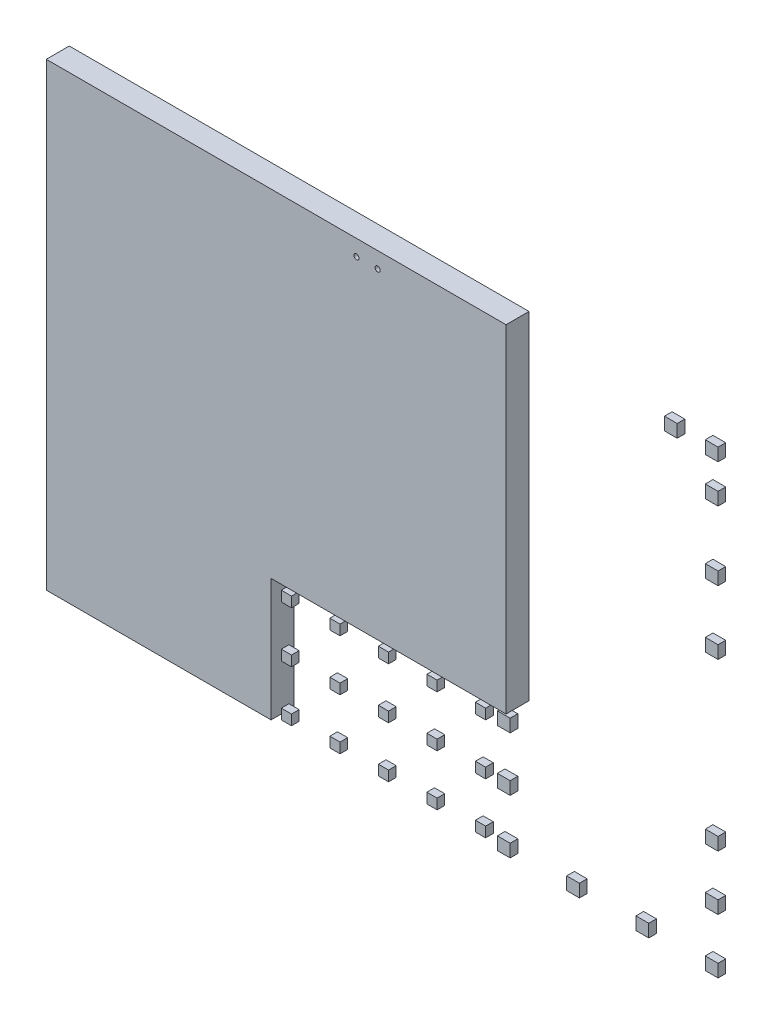
SolidWorks part; units mm, degrees
ref_plane "Спереди" through (0, 0, 0) normal (0, 0, 1) x (1, 0, 0)
ref_plane "Сверху" through (0, 0, 0) normal (0, 1, 0) x (1, 0, 0)
ref_plane "Справа" through (0, 0, 0) normal (1, 0, 0) x (0, 0, -1)
sketch "Эскиз1" plane through (0, 0, 0) normal (0, 0, 1) x (1, 0, 0)
  line L0 (0, 0) -> (9000, 0)
  line L1 (9000, 0) -> (9000, -6600)
  line L2 (9000, -6600) -> (4400, -6600)
  line L3 (4400, -6600) -> (4400, -9000)
  line L4 (4400, -9000) -> (0, -9000)
  line L5 (0, -9000) -> (0, 0)
  line L6 (8830, -6600) -> (8830, -9000) construction
  line L7 (8830, -9000) -> (9080, -9000)
  line L8 (8830, -9000) -> (8830, -8750)
  line L9 (8830, -8750) -> (9080, -8750)
  line L14 (9080, -9000) -> (9080, -8750)
  line L15 (9000, -203) -> (9000, -2700) construction
  line L16 (8797, -6600) -> (4400, -6600) construction
  line L17 (4400, -8797) -> (4400, -6603) construction
  line L18 (203, -9000) -> (4200, -9000) construction
  line L19 (8830, -6630) -> (9080, -6630)
  line L20 (8830, -6630) -> (8830, -6880)
  line L21 (8830, -6880) -> (9080, -6880)
  line L22 (9080, -6630) -> (9080, -6880)
  line L23 (9080, -6880) -> (9080, -7690) construction
  line L24 (8830, -7690) -> (9080, -7690)
  line L25 (8830, -7690) -> (8830, -7940)
  line L26 (8830, -7940) -> (9080, -7940)
  line L27 (9080, -7690) -> (9080, -7940)
  line L28 (9080, -7940) -> (9080, -8750) construction
  line L29 (13150, -9000) -> (0, -9000) construction
  line L30 (10186.6667, -8750) -> (10436.6667, -8750)
  line L31 (10186.6667, -8750) -> (10186.6667, -9000)
  line L32 (10186.6667, -9000) -> (10436.6667, -9000)
  line L33 (10436.6667, -8750) -> (10436.6667, -9000)
  line L34 (9080, -8750) -> (10186.6667, -8750) construction
  line L35 (11543.3333, -8750) -> (11793.3333, -8750)
  line L36 (11543.3333, -8750) -> (11543.3333, -9000)
  line L37 (11543.3333, -9000) -> (11793.3333, -9000)
  line L38 (11793.3333, -8750) -> (11793.3333, -9000)
  line L43 (12900, -8750) -> (13150, -8750)
  line L44 (12900, -8750) -> (12900, -9000)
  line L45 (12900, -9000) -> (13150, -9000)
  line L46 (13150, -8750) -> (13150, -9000)
  line L47 (10436.6667, -8750) -> (11543.3333, -8750) construction
  line L48 (11793.3333, -8750) -> (12900, -8750) construction
  line L49 (13150, -4500) -> (13150, -9000) construction
  line L50 (13150, -6600) -> (12900, -6600)
  line L51 (13150, -6600) -> (13150, -6850)
  line L52 (13150, -6850) -> (12900, -6850)
  line L53 (12900, -6600) -> (12900, -6850)
  line L54 (13150, -7675) -> (12900, -7675)
  line L55 (13150, -7675) -> (13150, -7925)
  line L56 (13150, -7925) -> (12900, -7925)
  line L57 (12900, -7675) -> (12900, -7925)
  line L58 (12900, -7675) -> (12900, -6850) construction
  line L59 (13150, -3600) -> (12900, -3600)
  line L60 (13150, -3600) -> (13150, -3350)
  line L61 (13150, -3350) -> (12900, -3350)
  line L62 (12900, -3600) -> (12900, -3350)
  line L63 (13150, -2100) -> (12900, -2100)
  line L64 (13150, -2100) -> (13150, -2350)
  line L65 (13150, -2350) -> (12900, -2350)
  line L66 (12900, -2100) -> (12900, -2350)
  line L67 (13150, -1000) -> (12900, -1000)
  line L68 (13150, -1000) -> (13150, -750)
  line L69 (13150, -750) -> (12900, -750)
  line L70 (12900, -1000) -> (12900, -750)
  line L71 (13150, 0) -> (12900, 0)
  line L72 (13150, 0) -> (13150, -250)
  line L73 (13150, -250) -> (12900, -250)
  line L74 (12900, 0) -> (12900, -250)
  line L75 (12100, 0) -> (12350, 0)
  line L76 (12100, 0) -> (12100, -250)
  line L77 (12100, -250) -> (12350, -250)
  line L78 (12350, 0) -> (12350, -250)
  line L79 (12900, -7925) -> (12900, -8750) construction
  line L80 (4800, -6900) -> (4800, -7700) construction
  line L81 (4600, -6700) -> (4800, -6700)
  line L82 (4600, -6700) -> (4600, -6900)
  line L83 (4600, -6900) -> (4800, -6900)
  line L84 (4800, -6700) -> (4800, -6900)
  line L85 (4600, -7700) -> (4800, -7700)
  line L86 (4600, -7700) -> (4600, -7900)
  line L87 (4600, -7900) -> (4800, -7900)
  line L88 (4800, -7700) -> (4800, -7900)
  line L89 (4600, -8700) -> (4800, -8700)
  line L90 (4600, -8700) -> (4600, -8900)
  line L91 (4600, -8900) -> (4800, -8900)
  line L92 (4800, -8700) -> (4800, -8900)
  line L93 (4800, -7900) -> (4800, -8700) construction
  line L94 (5550, -6700) -> (5550, -6900)
  line L95 (5550, -6700) -> (5750, -6700)
  line L96 (5750, -6700) -> (5750, -6900)
  line L97 (5550, -6900) -> (5750, -6900)
  line L98 (5550, -7700) -> (5550, -7900)
  line L99 (5550, -7700) -> (5750, -7700)
  line L100 (5750, -7700) -> (5750, -7900)
  line L101 (5550, -7900) -> (5750, -7900)
  line L102 (5550, -8700) -> (5550, -8900)
  line L103 (5550, -8700) -> (5750, -8700)
  line L104 (5750, -8700) -> (5750, -8900)
  line L105 (5550, -8900) -> (5750, -8900)
  line L106 (6500, -6700) -> (6500, -6900)
  line L107 (6500, -6700) -> (6700, -6700)
  line L108 (6700, -6700) -> (6700, -6900)
  line L109 (6500, -6900) -> (6700, -6900)
  line L110 (6500, -7700) -> (6500, -7900)
  line L111 (6500, -7700) -> (6700, -7700)
  line L112 (6700, -7700) -> (6700, -7900)
  line L113 (6500, -7900) -> (6700, -7900)
  line L114 (6500, -8700) -> (6500, -8900)
  line L115 (6500, -8700) -> (6700, -8700)
  line L116 (6700, -8700) -> (6700, -8900)
  line L117 (6500, -8900) -> (6700, -8900)
  line L118 (7450, -6700) -> (7450, -6900)
  line L119 (7450, -6700) -> (7650, -6700)
  line L120 (7650, -6700) -> (7650, -6900)
  line L121 (7450, -6900) -> (7650, -6900)
  line L122 (7450, -7700) -> (7450, -7900)
  line L123 (7450, -7700) -> (7650, -7700)
  line L124 (7650, -7700) -> (7650, -7900)
  line L125 (7450, -7900) -> (7650, -7900)
  line L126 (7450, -8700) -> (7450, -8900)
  line L127 (7450, -8700) -> (7650, -8700)
  line L128 (7650, -8700) -> (7650, -8900)
  line L129 (7450, -8900) -> (7650, -8900)
  line L130 (8400, -6700) -> (8400, -6900)
  line L131 (8400, -6700) -> (8600, -6700)
  line L132 (8600, -6700) -> (8600, -6900)
  line L133 (8400, -6900) -> (8600, -6900)
  line L134 (8400, -7700) -> (8400, -7900)
  line L135 (8400, -7700) -> (8600, -7700)
  line L136 (8600, -7700) -> (8600, -7900)
  line L137 (8400, -7900) -> (8600, -7900)
  line L138 (8400, -8700) -> (8400, -8900)
  line L139 (8400, -8700) -> (8600, -8700)
  line L140 (8600, -8700) -> (8600, -8900)
  line L141 (8400, -8900) -> (8600, -8900)
  circle A0 centre (6486.2448, -312.4922) radius 50
  circle A1 centre (6070.9439, -312.4922) radius 50
  dimension "D3" = 100
  dimension "D1" = 250
  dimension "D2" = 30
  dimension "D4" = 810
  dimension "D5" = 1106.6667
  dimension "D6" = 200
  dimension "D7" = 100
  dimension "D8" = 100
  dimension "D9" = 200
  dimension "D11" = 950
  dimension "D10" = 5
extrude "Бобышка-Вытянуть1" add sketch "Эскиз1" against normal blind 150
sketch "Эскиз2" plane through (0, 0, -150) normal (0, 0, -1) x (-1, 0, 0)
  line L0 (-450, -8550) -> (-450, -450)
  line L1 (-450, -450) -> (-8550, -450)
  line L2 (-8550, -450) -> (-8550, -6150)
  line L3 (-8550, -6150) -> (-3950, -6150)
  line L4 (-3950, -6150) -> (-3950, -8550)
  line L5 (-3950, -8550) -> (-450, -8550)
  line L6 (0, -9000) -> (0, 0)
  line L7 (0, 0) -> (-9000, 0)
  line L8 (-9000, 0) -> (-9000, -6600)
  line L9 (-9000, -6600) -> (-4400, -6600)
  line L10 (-4400, -6600) -> (-4400, -9000)
  line L11 (-4400, -9000) -> (0, -9000)
  line L12 (0, -9000) -> (0, 0)
  line L13 (0, 0) -> (-9000, 0)
  line L14 (-9000, 0) -> (-9000, -6600)
  line L15 (-9000, -6600) -> (-4400, -6600)
  line L16 (-4400, -6600) -> (-4400, -9000)
  line L17 (-4400, -9000) -> (0, -9000)
  dimension "D1" = 0
  dimension "D2" = 450
extrude "Бобышка-Вытянуть2" add sketch "Эскиз2" along normal blind 300
